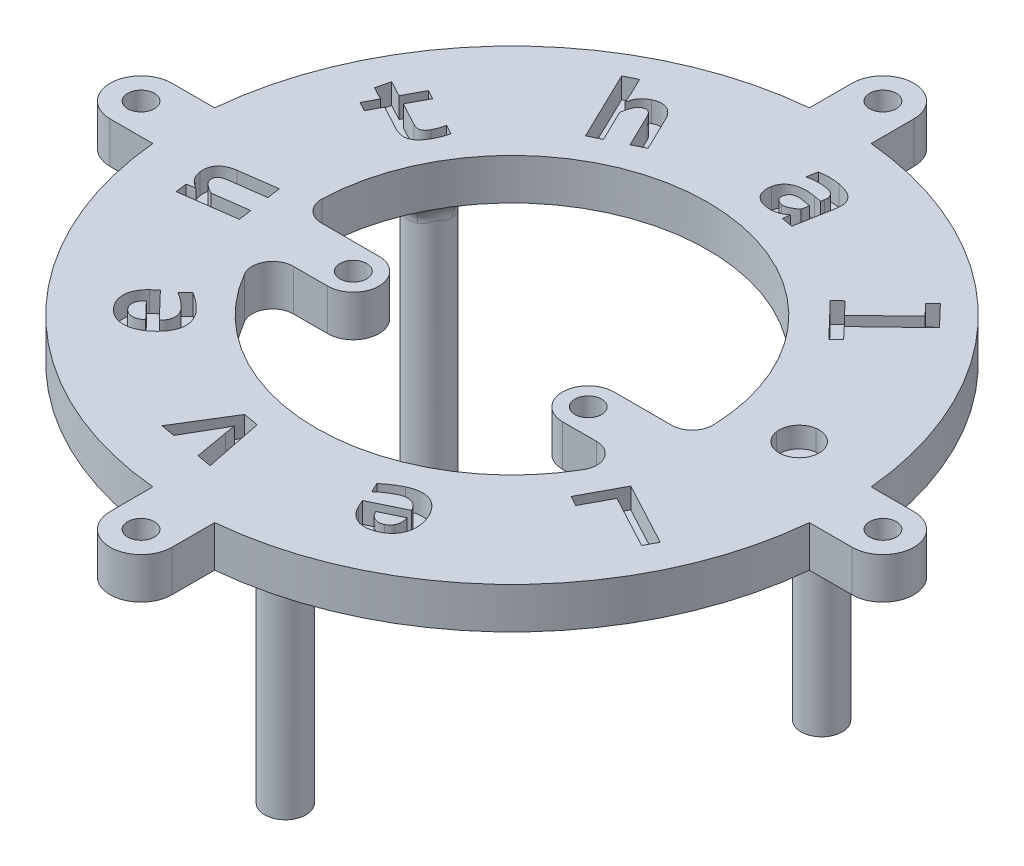
SolidWorks part; units mm, degrees
ref_plane "Front Plane" through (0, 0, 0) normal (0, 0, 1) x (1, 0, 0)
ref_plane "Top Plane" through (0, 0, 0) normal (0, 1, 0) x (1, 0, 0)
ref_plane "Right Plane" through (0, 0, 0) normal (1, 0, 0) x (0, 0, -1)
ref_axis "Center Axis" through (0, 0.65, 0) along (0, -1, 0)
sketch "STR Point" plane through (0, 0, 0) normal (0, 1, 0) x (1, 0, 0)
  point P0 (0.8, 2.9)
  dimension "D1" = 0.8
  dimension "D2" = 2.9
ref_axis "STR Axis" through (0.8, 0, -2.9) along (0, 1, 0)
sketch "Sketch1" plane through (0, 0, 0) normal (0, 1, 0) x (1, 0, 0)
  circle A0 centre (0, -11) radius 1
  dimension "D1" = 11
extrude "Boss-Extrude1" add sketch "Sketch1" against normal blind 13
sketch "Sketch2" plane through (0, 0, 0) normal (0, 1, 0) x (1, 0, 0)
  line L0 (5.7, -2) -> (9.2871, -2) construction
  line L1 (5.7, -0.75) -> (8.4963, -0.75)
  line L2 (5.7, -3.25) -> (7.3612, -3.25)
  line L3 (-18, 1.5) -> (-15.9295, 1.5)
  line L4 (-18, -1.5) -> (-15.9295, -1.5)
  line L5 (-5.7, -2) -> (-9.2871, -2) construction
  line L6 (-5.7, -3.25) -> (-7.3612, -3.25)
  line L7 (1.5, 18) -> (1.5, 15.9295)
  line L8 (-1.5, 18) -> (-1.5, 15.9295)
  line L9 (18, 1.5) -> (15.9295, 1.5)
  line L10 (18, -1.5) -> (15.9295, -1.5)
  line L11 (1.5, -18) -> (1.5, -15.9295)
  line L12 (-1.5, -18) -> (-1.5, -15.9295)
  line L13 (-5.7, -0.75) -> (-8.4963, -0.75)
  arc A0 (-15.9295, -1.5) -> (-1.5, -15.9295) centre (0, 0) ccw
  circle A1 centre (-5.7, -2) radius 0.65
  circle A2 centre (5.7, -2) radius 0.65
  arc A3 (-18, 1.5) -> (-18, -1.5) centre (-18, 0) ccw
  arc A4 (1.5, 18) -> (-1.5, 18) centre (0, 18) ccw
  arc A5 (18, -1.5) -> (18, 1.5) centre (18, 0) ccw
  arc A6 (-1.5, -18) -> (1.5, -18) centre (0, -18) ccw
  arc A7 (1.5, -15.9295) -> (15.9295, -1.5) centre (0, 0) ccw
  arc A8 (15.9295, 1.5) -> (1.5, 15.9295) centre (0, 0) ccw
  arc A9 (-1.5, 15.9295) -> (-15.9295, 1.5) centre (0, 0) ccw
  circle A10 centre (0, 18) radius 0.65
  circle A11 centre (18, 0) radius 0.65
  circle A12 centre (-18, 0) radius 0.65
  circle A13 centre (0, -18) radius 0.65
  arc A14 (-8.2272, -4.75) -> (8.2272, -4.75) centre (0, 0) ccw
  arc A15 (5.7, -0.75) -> (5.7, -3.25) centre (5.7, -2) ccw
  arc A16 (9.4959, 0.2794) -> (-9.4959, 0.2794) centre (0, 0) ccw
  arc A17 (-5.7, -3.25) -> (-5.7, -0.75) centre (-5.7, -2) ccw
  arc A18 (-7.3612, -3.25) -> (-8.2272, -4.75) centre (-7.3612, -4.25) ccw
  arc A19 (-8.4963, -0.75) -> (-9.4959, 0.2794) centre (-8.4963, 0.25) cw
  arc A20 (7.3612, -3.25) -> (8.2272, -4.75) centre (7.3612, -4.25) cw
  arc A21 (8.4963, -0.75) -> (9.4959, 0.2794) centre (8.4963, 0.25) ccw
  point P8 (7.4935, -2)
  point P37 (-7.4935, -2)
  point P50 (9.4703, -0.75)
  dimension "D1" = 5.7
  dimension "D2" = 2
  dimension "D5" = 1
  dimension "D4" = 1
  dimension "D3" = 5.7
extrude "Boss-Extrude2" add sketch "Sketch2" along normal blind 2
pattern_circular "CirPattern2" count 3 over 360 about axis through (0, 0.65, 0) along (0, -1, 0) of "Boss-Extrude1" reverse direction yes
fillet "Fillet1" radius 1 3 edges at (10.3923, 0, -6) (0, 0, 12) (-10.3923, 0, -6)
sketch "Sketch4" plane through (0, 2, 0) normal (0, 1, 0) x (1, 0, 0)
  circle A0 centre (0, 0) radius 11
sketch "Sketch3" plane through (0, 2, 0) normal (0, 1, 0) x (1, 0, 0)
  text T0 "Leventhal•" font "Consolas" height 3.5
extrude "Cut-Extrude1" cut sketch "Sketch3" against normal blind 1
